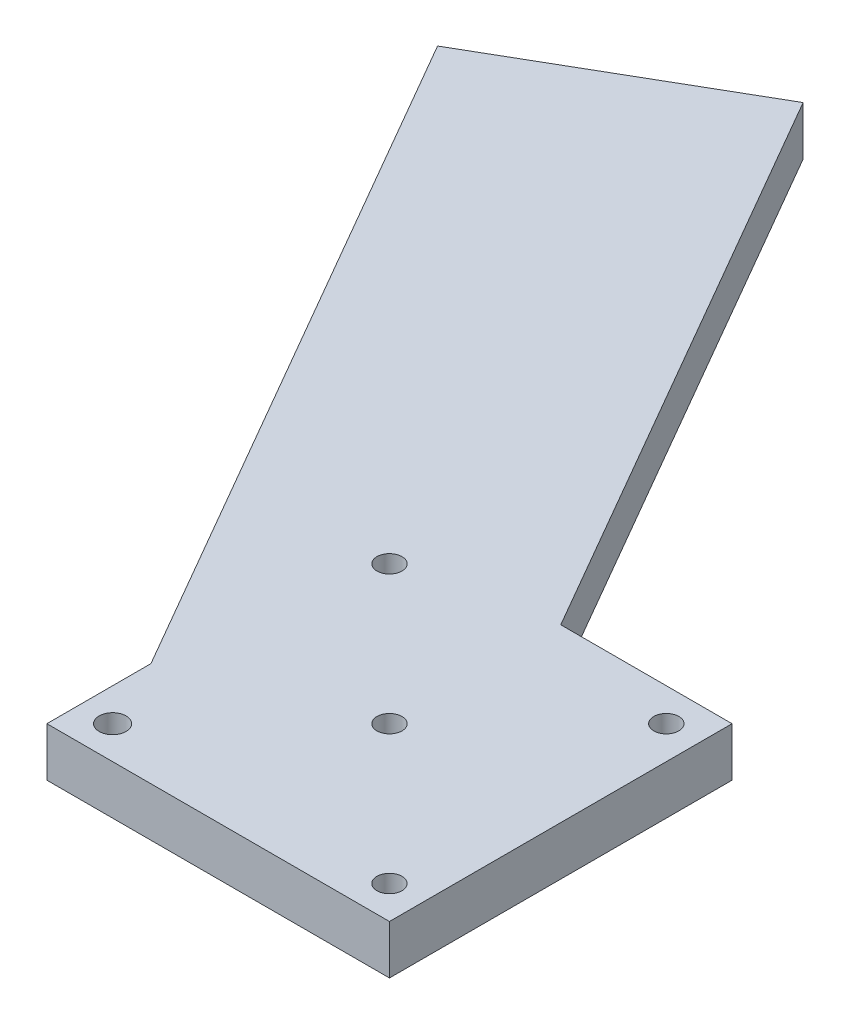
SolidWorks part; units mm, degrees
ref_plane "Front Plane" through (0, 0, 0) normal (0, 0, 1) x (1, 0, 0)
ref_plane "Top Plane" through (0, 0, 0) normal (0, 1, 0) x (1, 0, 0)
ref_plane "Right Plane" through (0, 0, 0) normal (1, 0, 0) x (0, 0, -1)
sketch "Sketch1" plane through (0, 0, 0) normal (0, 1, 0) x (1, 0, 0)
  line L0 (-22.0937, -22.0937) -> (22.3563, -22.0937)
  line L5 (22.3563, -22.0937) -> (22.3563, 22.3563)
  line L6 (22.3563, 22.3563) -> (-22.0937, 22.3563)
  line L7 (-22.0937, 22.3563) -> (-22.0937, -22.0937)
  line L8 (-72.8937, 79.3984) -> (-22.0937, -8.5898)
  line L9 (-42.8249, 96.7586) -> (0.1313, 22.3563)
  line L10 (-42.8249, 96.7586) -> (-72.8937, 79.3984)
  line L11 (22.3563, 22.3563) -> (-22.0937, -22.0937) construction
  circle A0 centre (-17.8292, 18.0918) radius 1.625
  circle A1 centre (0.1313, 0.1313) radius 1.625
  circle A2 centre (18.0918, -17.8292) radius 1.625
  circle A3 centre (-17.8292, -17.8292) radius 1.75
  circle A4 centre (18.0918, 18.0918) radius 1.625
  point P5 (-22.0937, -7.9599)
  point P18 (-63.7675, 70.5662)
  point P20 (-72.8937, 88.1961)
  point P21 (0.1313, 22.3563)
  point P22 (-22.0937, -12.3601)
  point P23 (0, 0)
  dimension "D6" = 3.5
  dimension "D1" = 101.6
  dimension "D2" = 30
  dimension "D3" = 90
  dimension "D4" = 44.45
  dimension "D5" = 38.1
extrude "Boss-Extrude1" add sketch "Sketch1" along normal blind 6.35 contours L10 L7 L6 | L6 L7 L0 L5 A4 A3 A2 A1 A0 | L5 L11 A4 A1 A3 L0 A2 region at (7.555, 0, 7.2678) region at (-7.2678, 0, -7.555) region at (-37.159, 0, -51.2905)
